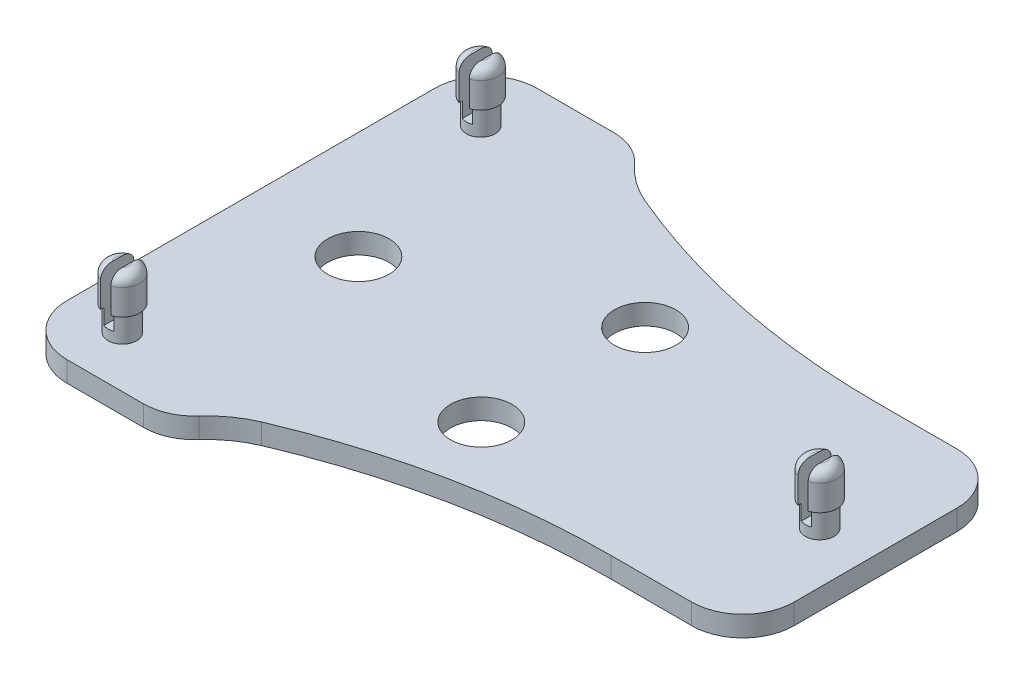
SolidWorks part; units mm, degrees
ref_plane "Front Plane" through (0, 0, 0) normal (0, 0, 1) x (1, 0, 0)
ref_plane "Top Plane" through (0, 0, 0) normal (0, 1, 0) x (1, 0, 0)
ref_plane "Right Plane" through (0, 0, 0) normal (1, 0, 0) x (0, 0, -1)
sketch "Sketch1" plane through (0, 0, 0) normal (0, 1, 0) x (1, 0, 0)
  line L0 (-30.5, -22.95) -> (-30.5, 22.95)
  line L1 (28.5, -20.95) -> (-28.5, -20.95) construction
  line L2 (28.5, -20.95) -> (28.5, 20.95) construction
  line L3 (28.5, 20.95) -> (-28.5, 20.95) construction
  line L4 (-28.5, -20.95) -> (-28.5, 20.95) construction
  line L5 (28.5, -20.95) -> (-28.5, 20.95) construction
  line L6 (28.5, 20.95) -> (-28.5, -20.95) construction
  line L7 (-15.5, 22.95) -> (-30.5, 22.95)
  line L8 (30.5, -12.95) -> (30.5, 12.95)
  line L9 (-15.5, -22.95) -> (-30.5, -22.95)
  line L10 (0, 0) -> (-42.2176, 0) construction
  line L11 (-15.5, 22.95) -> (-15.5, 11.3939) construction
  line L12 (30.5, 12.95) -> (17.6169, 12.95) construction
  line L13 (17.6169, 12.95) -> (-11.7527, 12.95) construction
  line L14 (-15.5, 22.95) -> (-15.5, 20.95)
  line L15 (17.6169, 12.95) -> (30.5, 12.95)
  line L16 (17.6169, -12.95) -> (30.5, -12.95)
  line L17 (-15.5, -22.95) -> (-15.5, -20.95)
  line L18 (30.5, 22.95) -> (-30.5, 22.95) construction
  line L19 (30.5, -22.95) -> (30.5, 22.95) construction
  line L20 (30.5, -22.95) -> (-30.5, -22.95) construction
  circle A2 centre (25.5, -0.45) radius 1.6
  arc A3 (-15.5, 20.95) -> (17.6169, 12.95) centre (17.6169, 85.4958) ccw
  arc A4 (-15.5, -20.95) -> (17.6169, -12.95) centre (17.6169, -85.4958) cw
  point P0 (0, 0)
  dimension "D7" = 3
  dimension "D8" = 20.5
  dimension "D1" = 41.9
  dimension "D2" = 57
  dimension "D9" = 15
  dimension "D10" = 10
  dimension "D3" = 2
extrude "Boss-Extrude1" add sketch "Sketch1" along normal blind 2
fillet "Fillet1" radius 10 2 edges at (-15.5, 1, 20.95) (-15.5, 1, -20.95)
fillet "Fillet2" radius 5 6 edges at (-30.5, 1, -22.95) (-30.5, 1, 22.95) (-15.5, 1, 22.95) (-15.5, 1, -22.95) (30.5, 1, -12.95) (30.5, 1, 12.95)
ref_plane "Plane1" through (-15.5, 0, 0) normal (-1, 0, 0) x (0, 0, 1)
sketch "Sketch5" plane through (0, 2, 0) normal (0, 1, 0) x (1, 0, 0)
  circle A0 centre (-25.1, 17.05) radius 1.4
  circle A1 centre (-25.1, -17.95) radius 1.4
  circle A2 centre (25.5, -0.45) radius 1.4
extrude "Boss-Extrude6" add sketch "Sketch5" along normal blind 6
sketch "Sketch6" plane through (0, 8, 0) normal (0, 1, 0) x (1, 0, 0)
  circle A0 centre (-25.1, 17.05) radius 1.7
  circle A1 centre (25.5, -0.45) radius 1.7
  circle A2 centre (-25.1, -17.95) radius 1.7
extrude "Boss-Extrude7" add sketch "Sketch6" against normal blind 3.5
fillet "Fillet4" radius 1 2 edges at (-25.1, 8, 19.65) (-25.1, 8, -15.35)
fillet "Fillet5" radius 1 1 edges at (25.5, 8, 2.15)
sketch "Sketch7" plane through (0, 8, 0) normal (0, 1, 0) x (1, 0, 0)
  line L1 (-24.6, 19.7752) -> (-25.6, 19.7752)
  line L2 (-24.6, 19.7752) -> (-24.6, 14.3248)
  line L3 (-24.6, 14.3248) -> (-25.6, 14.3248)
  line L4 (-25.6, 19.7752) -> (-25.6, 14.3248)
  line L5 (-24.6, 19.7752) -> (-25.6, 14.3248) construction
  line L6 (-24.6, 14.3248) -> (-25.6, 19.7752) construction
  line L7 (-24.6, -15.6084) -> (-25.6, -15.6084)
  line L8 (-24.6, -15.6084) -> (-24.6, -20.2916)
  line L9 (-24.6, -20.2916) -> (-25.6, -20.2916)
  line L10 (-25.6, -15.6084) -> (-25.6, -20.2916)
  line L11 (-24.6, -15.6084) -> (-25.6, -20.2916) construction
  line L12 (-24.6, -20.2916) -> (-25.6, -15.6084) construction
  line L13 (26, 2.4829) -> (25, 2.4829)
  line L14 (26, 2.4829) -> (26, -3.3829)
  line L15 (26, -3.3829) -> (25, -3.3829)
  line L16 (25, 2.4829) -> (25, -3.3829)
  line L17 (26, 2.4829) -> (25, -3.3829) construction
  line L18 (26, -3.3829) -> (25, 2.4829) construction
  point P0 (-25.1, 17.05)
  point P6 (-25.1, -17.95)
  point P12 (25.5, -0.45)
extrude "Cut-Extrude3" cut sketch "Sketch7" against normal blind 5
sketch "Sketch8" plane through (0, 0, 0) normal (0, -1, 0) x (1, 0, 0)
  circle A0 centre (25.5, 0.45) radius 1.6
extrude "Boss-Extrude8" add sketch "Sketch8" against normal blind 2
sketch "Sketch10" plane through (0, 2, 0) normal (0, 1, 0) x (1, 0, 0)
  line L0 (-20, 0) -> (0, 0) construction
  line L1 (0, 0) -> (0, 8) construction
  circle A0 centre (-20, 0) radius 3
  circle A1 centre (0, 8) radius 3
  circle A2 centre (0, -8) radius 3
extrude "Cut-Extrude4" cut sketch "Sketch10" against normal blind 10
